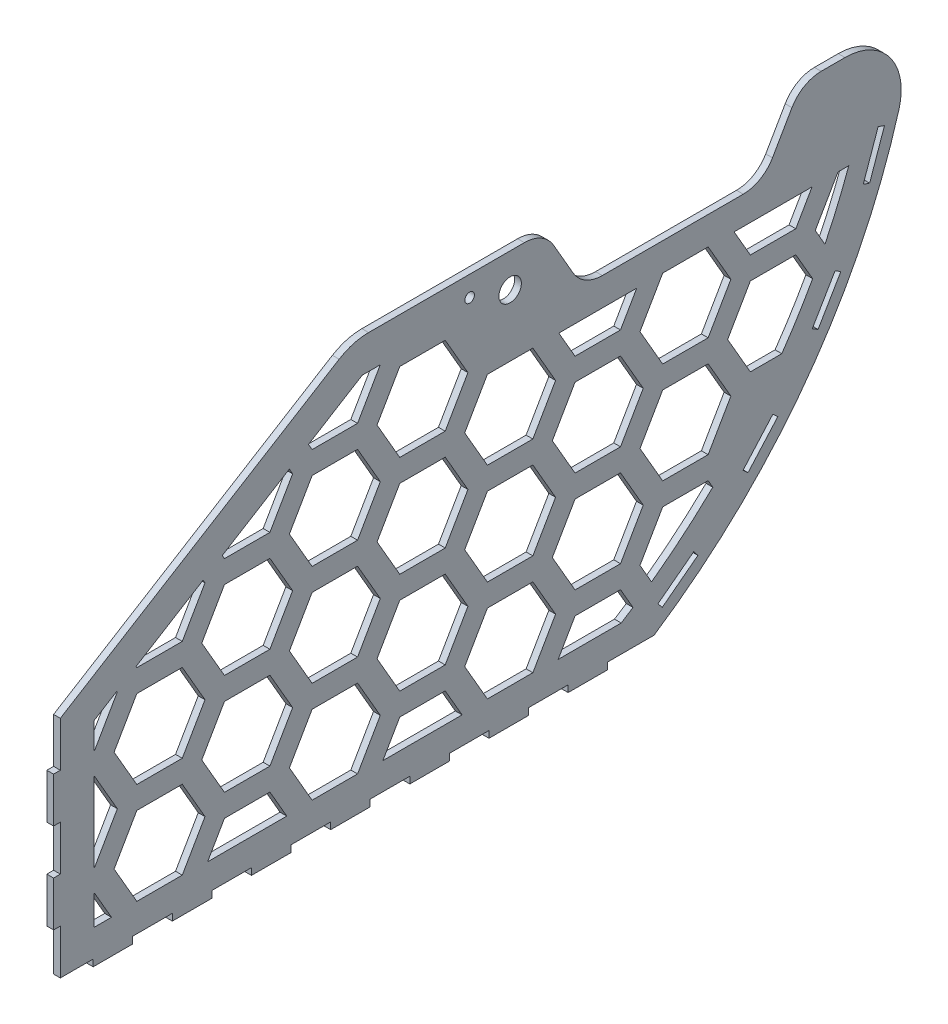
SolidWorks part; units mm, degrees
ref_plane "Front Plane" through (0, 0, 0) normal (0, 0, 1) x (1, 0, 0)
ref_plane "Top Plane" through (0, 0, 0) normal (0, 1, 0) x (1, 0, 0)
ref_plane "Right Plane" through (0, 0, 0) normal (1, 0, 0) x (0, 0, -1)
sketch "Sketch1" plane through (0, 0, 0) normal (1, 0, 0) x (0, 0, -1)
  line L0 (-190, -90) -> (-190, 90)
  line L1 (-190, 90) -> (190, 90)
  line L2 (-190, -90) -> (74, -90)
  line L3 (-193, -93) -> (-175.4, -93) construction
  line L4 (-175.4, -93) -> (-157.8, -93)
  line L5 (-175.4, -93) -> (-175.4, -90)
  line L6 (-175.4, -90) -> (-157.8, -90)
  line L7 (-157.8, -93) -> (-157.8, -90)
  line L8 (-175.4, -93) -> (-157.8, -90) construction
  line L9 (-175.4, -90) -> (-157.8, -93) construction
  line L10 (-140.2, -93) -> (-122.6, -93)
  line L11 (-140.2, -93) -> (-140.2, -90)
  line L12 (-140.2, -90) -> (-122.6, -90)
  line L13 (-122.6, -93) -> (-122.6, -90)
  line L14 (-140.2, -93) -> (-122.6, -90) construction
  line L15 (-140.2, -90) -> (-122.6, -93) construction
  line L16 (-105, -93) -> (-87.4, -93)
  line L17 (-105, -93) -> (-105, -90)
  line L18 (-105, -90) -> (-87.4, -90)
  line L19 (-87.4, -93) -> (-87.4, -90)
  line L20 (-105, -93) -> (-87.4, -90) construction
  line L21 (-105, -90) -> (-87.4, -93) construction
  line L22 (-69.8, -93) -> (-52.2, -93)
  line L23 (-69.8, -93) -> (-69.8, -90)
  line L24 (-69.8, -90) -> (-52.2, -90)
  line L25 (-52.2, -93) -> (-52.2, -90)
  line L26 (-69.8, -93) -> (-52.2, -90) construction
  line L27 (-69.8, -90) -> (-52.2, -93) construction
  line L28 (-34.6, -93) -> (-17, -93)
  line L29 (-34.6, -93) -> (-34.6, -90)
  line L30 (-34.6, -90) -> (-17, -90)
  line L31 (-17, -93) -> (-17, -90)
  line L32 (-34.6, -93) -> (-17, -90) construction
  line L33 (-34.6, -90) -> (-17, -93) construction
  line L34 (0.6, -93) -> (18.2, -93)
  line L35 (0.6, -93) -> (0.6, -90)
  line L36 (0.6, -90) -> (18.2, -90)
  line L37 (18.2, -93) -> (18.2, -90)
  line L38 (0.6, -93) -> (18.2, -90) construction
  line L39 (0.6, -90) -> (18.2, -93) construction
  line L40 (35.8, -93) -> (53.4, -93)
  line L41 (35.8, -93) -> (35.8, -90)
  line L42 (35.8, -90) -> (53.4, -90)
  line L43 (53.4, -93) -> (53.4, -90)
  line L44 (35.8, -93) -> (53.4, -90) construction
  line L45 (35.8, -90) -> (53.4, -93) construction
  line L46 (-157.8, -93) -> (-140.2, -93) construction
  line L47 (-122.6, -93) -> (-105, -93) construction
  line L48 (-87.4, -93) -> (-69.8, -93) construction
  line L49 (-52.2, -93) -> (-34.6, -93) construction
  line L50 (-17, -93) -> (0.6, -93) construction
  line L51 (18.2, -93) -> (35.8, -93) construction
  line L52 (53.4, -93) -> (71, -93) construction
  line L53 (-193, -90) -> (-193, -70) construction
  line L54 (-193, -30) -> (-190, -30)
  line L55 (-193, -30) -> (-193, -10)
  line L56 (-193, -10) -> (-190, -10)
  line L57 (-190, -30) -> (-190, -10)
  line L58 (-193, -30) -> (-190, -10) construction
  line L59 (-193, -10) -> (-190, -30) construction
  line L60 (-193, -70) -> (-190, -70)
  line L61 (-193, -70) -> (-193, -50)
  line L62 (-193, -50) -> (-190, -50)
  line L63 (-190, -70) -> (-190, -50)
  line L64 (-193, -70) -> (-190, -50) construction
  line L65 (-193, -50) -> (-190, -70) construction
  line L66 (-193, -50) -> (-193, -30) construction
  line L67 (-193, -10) -> (-193, 10) construction
  line L68 (-190, 10) -> (-60, 90)
  arc A0 (74, -90) -> (190, 90) centre (-71.9803, 131.454) ccw
  point P5 (-190, 0)
  point P6 (-96.2, -91.5)
  point P8 (0, 90)
  point P9 (-131.4, -91.5)
  point P17 (-166.6, -91.5)
  point P23 (-61, -91.5)
  point P28 (-25.8, -91.5)
  point P33 (9.4, -91.5)
  point P38 (44.6, -91.5)
  point P44 (-191.5, -60)
  point P47 (-191.5, -20)
  dimension "D1" = 180
  dimension "D2" = 380
  dimension "D3" = 264
  dimension "D4" = 3
  dimension "D5" = 100
  dimension "D6" = 3
  dimension "D7" = 130
extrude "Boss-Extrude1" add sketch "Sketch1" along normal mid plane 3 contours L2 A0 L1 L0 | L56 L55 L54 L0 | L62 L61 L60 L0 | L4 L7 L2 L5 | L10 L13 L2 L11 | L16 L19 L2 L17 | L22 L25 L2 L23 | L28 L31 L2 L29 | L40 L43 L2 L41 | L34 L37 L2 L35 region at (0, -0.5729, 6.488) region at (0, -60, 191.5) region at (0, -91.5, 166.6) region at (0, -20, 191.5) region at (0, -91.5, 131.4) region at (0, -91.5, 96.2) region at (0, -91.5, 61) region at (0, -91.5, -44.6) region at (0, -91.5, 25.8) region at (0, -91.5, -9.4)
sketch "Sketch3" plane through (1.5, 0, 0) normal (1, 0, 0) x (0, 0, -1)
  line L0 (144.3362, -7.1911) -> (154.4649, 10.0544)
  line L1 (144.3362, -7.1911) -> (146.923, -8.7104)
  line L2 (154.4649, 10.0544) -> (157.0517, 8.5351)
  line L3 (146.923, -8.7104) -> (157.0517, 8.5351)
  line L4 (144.3362, -7.1911) -> (157.0517, 8.5351) construction
  line L5 (154.4649, 10.0544) -> (146.923, -8.7104) construction
  line L6 (169.8454, 36.1385) -> (176.458, 55.0137)
  line L7 (169.8454, 36.1385) -> (167.0141, 37.1304)
  line L8 (176.458, 55.0137) -> (173.6268, 56.0056)
  line L9 (167.0141, 37.1304) -> (173.6268, 56.0056)
  line L10 (169.8454, 36.1385) -> (173.6268, 56.0056) construction
  line L11 (176.458, 55.0137) -> (167.0141, 37.1304) construction
  line L12 (115.7814, -48.2966) -> (129.046, -33.3282)
  line L13 (115.7814, -48.2966) -> (113.5362, -46.3069)
  line L14 (129.046, -33.3282) -> (126.8007, -31.3385)
  line L15 (113.5362, -46.3069) -> (126.8007, -31.3385)
  line L16 (115.7814, -48.2966) -> (126.8007, -31.3385) construction
  line L17 (129.046, -33.3282) -> (113.5362, -46.3069) construction
  line L18 (75.7706, -78.7482) -> (91.6729, -66.6191)
  line L19 (75.7706, -78.7482) -> (77.5899, -81.1336)
  line L20 (91.6729, -66.6191) -> (93.4922, -69.0044)
  line L21 (77.5899, -81.1336) -> (93.4922, -69.0044)
  line L22 (75.7706, -78.7482) -> (93.4922, -69.0044) construction
  line L23 (91.6729, -66.6191) -> (77.5899, -81.1336) construction
  line L24 (84.6314, -73.8763) -> (121.2911, -39.8175) construction
  line L25 (121.2911, -39.8175) -> (150.694, 0.672) construction
  line L26 (150.694, 0.672) -> (171.7361, 46.072) construction
  line L27 (150.694, 0.672) -> (156.7299, -2.873) construction
  line L28 (121.2911, -39.8175) -> (126.53, -44.4601) construction
  line L29 (84.6314, -73.8763) -> (88.8766, -79.4421) construction
  line L30 (171.7361, 46.072) -> (178.3424, 43.7576) construction
  line L31 (80.9255, -85.5067) -> (96.8278, -73.3775) construction
  line L32 (119.8977, -51.9443) -> (133.1623, -36.9759) construction
  line L33 (151.6655, -11.4958) -> (161.7943, 5.7497) construction
  line L34 (181.6487, 53.1952) -> (175.0361, 34.32) construction
  line L35 (84.6314, -73.8763) -> (65.5, -90) construction
  line L36 (171.7361, 46.072) -> (181.5, 90) construction
  line L37 (53.4, -90) -> (74, -90) construction
  line L38 (-60, 90) -> (190, 90) construction
  line L39 (181.5, 90) -> (190, 90) construction
  line L40 (65.5, -90) -> (74, -90) construction
  line L41 (84.6314, -73.8763) -> (102.9612, -56.8469) construction
  arc A0 (74, -90) -> (190, 90) centre (-71.9803, 131.454) ccw construction
  point P1 (150.694, 0.672)
  point P2 (171.7361, 46.072)
  point P3 (121.2911, -39.8175)
  point P8 (84.6314, -73.8763)
  point P37 (178.3424, 43.7576)
  point P39 (156.7299, -2.873)
  point P43 (126.53, -44.4601)
  point P44 (88.8766, -79.4421)
  dimension "D4" = 8.5
  dimension "D1" = 3
  dimension "D2" = 7
  dimension "D3" = 20
  dimension "D5" = 45
extrude "Cut-Extrude2" cut sketch "Sketch3" against normal through all both and the other way through all
fillet "Fillet1" radius 25 2 edges at (0, 90, -190) (0, 90, 60)
sketch "Sketch4" plane through (1.5, 0, 0) normal (1, 0, 0) x (0, 0, -1)
  circle A0 centre (10, 75) radius 5
  circle A1 centre (-8, 81) radius 2.15
  arc A2 (182.91, 58.0846) -> (158.8854, 90) centre (158.8854, 65) ccw construction
  dimension "D1" = 10
  dimension "D4" = 4.3
  dimension "D6" = 6
  dimension "D2" = 148.8854
  dimension "D3" = 75
  dimension "D5" = 18
extrude "Cut-Extrude3" cut sketch "Sketch4" against normal through all both and the other way through all
sketch "Sketch5" plane through (1.5, 0, 0) normal (1, 0, 0) x (0, 0, -1)
  line L0 (25, 90) -> (42.3205, 60)
  line L1 (-52.9239, 90) -> (158.8854, 90) construction
  line L2 (42.3205, 60) -> (122.3205, 60)
  line L3 (122.3205, 60) -> (139.641, 90)
  circle A0 centre (10, 75) radius 5 construction
  point P8 (136.2989, 70.4297)
  dimension "D1" = 60
  dimension "D2" = 80
  dimension "D3" = 15
  dimension "D4" = 30
extrude "Cut-Extrude5" cut sketch "Sketch5" against normal through all both and the other way through all
sketch "Sketch2" plane through (0, 0, 0) normal (1, 0, 0) x (0, 0, -1)
  line L0 (-96.8098, -20) -> (-117.0171, -20)
  line L1 (-96.8098, -65) -> (-117.0171, -65)
  line L2 (-117.0171, -65) -> (-127.1207, -82.5)
  line L3 (-127.1207, -82.5) -> (-117.0171, -100)
  line L4 (-117.0171, -100) -> (-96.8098, -100)
  line L5 (-96.8098, -100) -> (-86.7062, -82.5)
  line L6 (-86.7062, -82.5) -> (-96.8098, -65)
  line L13 (-117.0171, -20) -> (-127.1207, -37.5)
  line L14 (-88.1495, -105) -> (-78.0459, -122.5)
  line L15 (-78.0459, -122.5) -> (-57.8387, -122.5)
  line L16 (-57.8387, -122.5) -> (-47.735, -105)
  line L17 (-47.735, -105) -> (-57.8387, -87.5)
  line L18 (-57.8387, -87.5) -> (-78.0459, -87.5)
  line L19 (-78.0459, -87.5) -> (-88.1495, -105)
  line L20 (-127.1207, -37.5) -> (-117.0171, -55)
  line L21 (-117.0171, -55) -> (-96.8098, -55)
  line L22 (-96.8098, -55) -> (-86.7062, -37.5)
  line L23 (-86.7062, -37.5) -> (-96.8098, -20)
  line L24 (-88.1495, -60) -> (-78.0459, -77.5)
  line L25 (-78.0459, -77.5) -> (-57.8387, -77.5)
  line L26 (-57.8387, -77.5) -> (-47.735, -60)
  line L27 (-47.735, -60) -> (-57.8387, -42.5)
  line L28 (-57.8387, -42.5) -> (-78.0459, -42.5)
  line L29 (-78.0459, -42.5) -> (-88.1495, -60)
  line L30 (-96.8098, 25) -> (-117.0171, 25)
  line L31 (-117.0171, 25) -> (-127.1207, 7.5)
  line L32 (-127.1207, 7.5) -> (-117.0171, -10)
  line L33 (-117.0171, -10) -> (-96.8098, -10)
  line L34 (-96.8098, -10) -> (-86.7062, 7.5)
  line L35 (-86.7062, 7.5) -> (-96.8098, 25)
  line L36 (-88.1495, -15) -> (-78.0459, -32.5)
  line L37 (-78.0459, -32.5) -> (-57.8387, -32.5)
  line L38 (-57.8387, -32.5) -> (-47.735, -15)
  line L39 (-47.735, -15) -> (-57.8387, 2.5)
  line L40 (-57.8387, 2.5) -> (-78.0459, 2.5)
  line L41 (-78.0459, 2.5) -> (-88.1495, -15)
  line L42 (-96.8098, 70) -> (-117.0171, 70)
  line L43 (-117.0171, 70) -> (-127.1207, 52.5)
  line L44 (-127.1207, 52.5) -> (-117.0171, 35)
  line L45 (-117.0171, 35) -> (-96.8098, 35)
  line L46 (-96.8098, 35) -> (-86.7062, 52.5)
  line L47 (-86.7062, 52.5) -> (-96.8098, 70)
  line L48 (-88.1495, 30) -> (-78.0459, 12.5)
  line L49 (-78.0459, 12.5) -> (-57.8387, 12.5)
  line L50 (-57.8387, 12.5) -> (-47.735, 30)
  line L51 (-47.735, 30) -> (-57.8387, 47.5)
  line L52 (-57.8387, 47.5) -> (-78.0459, 47.5)
  line L53 (-78.0459, 47.5) -> (-88.1495, 30)
  line L54 (-96.8098, 115) -> (-117.0171, 115)
  line L55 (-117.0171, 115) -> (-127.1207, 97.5)
  line L56 (-127.1207, 97.5) -> (-117.0171, 80)
  line L57 (-117.0171, 80) -> (-96.8098, 80)
  line L58 (-96.8098, 80) -> (-86.7062, 97.5)
  line L59 (-86.7062, 97.5) -> (-96.8098, 115)
  line L60 (-88.1495, 75) -> (-78.0459, 57.5)
  line L61 (-78.0459, 57.5) -> (-57.8387, 57.5)
  line L62 (-57.8387, 57.5) -> (-47.735, 75)
  line L63 (-47.735, 75) -> (-57.8387, 92.5)
  line L64 (-57.8387, 92.5) -> (-78.0459, 92.5)
  line L65 (-78.0459, 92.5) -> (-88.1495, 75)
  line L66 (-96.8098, 160) -> (-117.0171, 160)
  line L67 (-117.0171, 160) -> (-127.1207, 142.5)
  line L68 (-127.1207, 142.5) -> (-117.0171, 125)
  line L69 (-117.0171, 125) -> (-96.8098, 125)
  line L70 (-96.8098, 125) -> (-86.7062, 142.5)
  line L71 (-86.7062, 142.5) -> (-96.8098, 160)
  line L72 (-88.1495, 120) -> (-78.0459, 102.5)
  line L73 (-78.0459, 102.5) -> (-57.8387, 102.5)
  line L74 (-57.8387, 102.5) -> (-47.735, 120)
  line L75 (-47.735, 120) -> (-57.8387, 137.5)
  line L76 (-57.8387, 137.5) -> (-78.0459, 137.5)
  line L77 (-78.0459, 137.5) -> (-88.1495, 120)
  line L102 (-96.8098, -65) -> (-96.8098, -20) construction
  line L103 (-78.0459, -87.5) -> (-78.0459, -77.5) construction
  line L104 (-91.758, -73.75) -> (-83.0977, -68.75) construction
  line L105 (-10.2073, 120) -> (-0.1036, 102.5)
  line L106 (-0.1036, 102.5) -> (20.1036, 102.5)
  line L107 (20.1036, 102.5) -> (30.2073, 120)
  line L108 (30.2073, 120) -> (20.1036, 137.5)
  line L109 (20.1036, 137.5) -> (-0.1036, 137.5)
  line L110 (-0.1036, 137.5) -> (-10.2073, 120)
  line L111 (-18.8675, 160) -> (-39.0748, 160)
  line L112 (-39.0748, 160) -> (-49.1784, 142.5)
  line L113 (-49.1784, 142.5) -> (-39.0748, 125)
  line L114 (-39.0748, 125) -> (-18.8675, 125)
  line L115 (-18.8675, 125) -> (-8.7639, 142.5)
  line L116 (-8.7639, 142.5) -> (-18.8675, 160)
  line L117 (-18.8675, 115) -> (-39.0748, 115)
  line L118 (-39.0748, 115) -> (-49.1784, 97.5)
  line L119 (-49.1784, 97.5) -> (-39.0748, 80)
  line L120 (-39.0748, 80) -> (-18.8675, 80)
  line L121 (-18.8675, 80) -> (-8.7639, 97.5)
  line L122 (-8.7639, 97.5) -> (-18.8675, 115)
  line L123 (-18.8675, 70) -> (-39.0748, 70)
  line L124 (-39.0748, 70) -> (-49.1784, 52.5)
  line L125 (-49.1784, 52.5) -> (-39.0748, 35)
  line L126 (-39.0748, 35) -> (-18.8675, 35)
  line L127 (-18.8675, 35) -> (-8.7639, 52.5)
  line L128 (-8.7639, 52.5) -> (-18.8675, 70)
  line L129 (-18.8675, 25) -> (-39.0748, 25)
  line L130 (-39.0748, 25) -> (-49.1784, 7.5)
  line L131 (-49.1784, 7.5) -> (-39.0748, -10)
  line L132 (-39.0748, -10) -> (-18.8675, -10)
  line L133 (-18.8675, -10) -> (-8.7639, 7.5)
  line L134 (-8.7639, 7.5) -> (-18.8675, 25)
  line L135 (-10.2073, -15) -> (-0.1036, -32.5)
  line L136 (-0.1036, -32.5) -> (20.1036, -32.5)
  line L137 (20.1036, -32.5) -> (30.2073, -15)
  line L138 (30.2073, -15) -> (20.1036, 2.5)
  line L139 (20.1036, 2.5) -> (-0.1036, 2.5)
  line L140 (-0.1036, 2.5) -> (-10.2073, -15)
  line L141 (-18.8675, -20) -> (-39.0748, -20)
  line L142 (-39.0748, -20) -> (-49.1784, -37.5)
  line L143 (-49.1784, -37.5) -> (-39.0748, -55)
  line L144 (-39.0748, -55) -> (-18.8675, -55)
  line L145 (-18.8675, -55) -> (-8.7639, -37.5)
  line L146 (-8.7639, -37.5) -> (-18.8675, -20)
  line L147 (-10.2073, -60) -> (-0.1036, -77.5)
  line L148 (-0.1036, -77.5) -> (20.1036, -77.5)
  line L149 (20.1036, -77.5) -> (30.2073, -60)
  line L150 (30.2073, -60) -> (20.1036, -42.5)
  line L151 (20.1036, -42.5) -> (-0.1036, -42.5)
  line L152 (-0.1036, -42.5) -> (-10.2073, -60)
  line L153 (-18.8675, -65) -> (-39.0748, -65)
  line L154 (-39.0748, -65) -> (-49.1784, -82.5)
  line L155 (-49.1784, -82.5) -> (-39.0748, -100)
  line L156 (-39.0748, -100) -> (-18.8675, -100)
  line L157 (-18.8675, -100) -> (-8.7639, -82.5)
  line L158 (-8.7639, -82.5) -> (-18.8675, -65)
  line L159 (-10.2073, -105) -> (-0.1036, -122.5)
  line L160 (-0.1036, -122.5) -> (20.1036, -122.5)
  line L161 (20.1036, -122.5) -> (30.2073, -105)
  line L162 (30.2073, -105) -> (20.1036, -87.5)
  line L163 (20.1036, -87.5) -> (-0.1036, -87.5)
  line L164 (-0.1036, -87.5) -> (-10.2073, -105)
  line L165 (-10.2073, 30) -> (-0.1036, 12.5)
  line L166 (-0.1036, 12.5) -> (20.1036, 12.5)
  line L167 (20.1036, 12.5) -> (30.2073, 30)
  line L168 (30.2073, 30) -> (20.1036, 47.5)
  line L169 (20.1036, 47.5) -> (-0.1036, 47.5)
  line L170 (-0.1036, 47.5) -> (-10.2073, 30)
  line L171 (-10.2073, 75) -> (-0.1036, 57.5)
  line L172 (-0.1036, 57.5) -> (20.1036, 57.5)
  line L173 (20.1036, 57.5) -> (30.2073, 75)
  line L174 (30.2073, 75) -> (20.1036, 92.5)
  line L175 (20.1036, 92.5) -> (-0.1036, 92.5)
  line L176 (-0.1036, 92.5) -> (-10.2073, 75)
  line L177 (67.735, 120) -> (77.8387, 102.5)
  line L178 (77.8387, 102.5) -> (98.0459, 102.5)
  line L179 (98.0459, 102.5) -> (108.1495, 120)
  line L180 (108.1495, 120) -> (98.0459, 137.5)
  line L181 (98.0459, 137.5) -> (77.8387, 137.5)
  line L182 (77.8387, 137.5) -> (67.735, 120)
  line L183 (59.0748, 160) -> (38.8675, 160)
  line L184 (38.8675, 160) -> (28.7639, 142.5)
  line L185 (28.7639, 142.5) -> (38.8675, 125)
  line L186 (38.8675, 125) -> (59.0748, 125)
  line L187 (59.0748, 125) -> (69.1784, 142.5)
  line L188 (69.1784, 142.5) -> (59.0748, 160)
  line L189 (59.0748, 115) -> (38.8675, 115)
  line L190 (38.8675, 115) -> (28.7639, 97.5)
  line L191 (28.7639, 97.5) -> (38.8675, 80)
  line L192 (38.8675, 80) -> (59.0748, 80)
  line L193 (59.0748, 80) -> (69.1784, 97.5)
  line L194 (69.1784, 97.5) -> (59.0748, 115)
  line L195 (59.0748, 70) -> (38.8675, 70)
  line L196 (38.8675, 70) -> (28.7639, 52.5)
  line L197 (28.7639, 52.5) -> (38.8675, 35)
  line L198 (38.8675, 35) -> (59.0748, 35)
  line L199 (59.0748, 35) -> (69.1784, 52.5)
  line L200 (69.1784, 52.5) -> (59.0748, 70)
  line L201 (59.0748, 25) -> (38.8675, 25)
  line L202 (38.8675, 25) -> (28.7639, 7.5)
  line L203 (28.7639, 7.5) -> (38.8675, -10)
  line L204 (38.8675, -10) -> (59.0748, -10)
  line L205 (59.0748, -10) -> (69.1784, 7.5)
  line L206 (69.1784, 7.5) -> (59.0748, 25)
  line L207 (67.735, -15) -> (77.8387, -32.5)
  line L208 (77.8387, -32.5) -> (98.0459, -32.5)
  line L209 (98.0459, -32.5) -> (108.1495, -15)
  line L210 (108.1495, -15) -> (98.0459, 2.5)
  line L211 (98.0459, 2.5) -> (77.8387, 2.5)
  line L212 (77.8387, 2.5) -> (67.735, -15)
  line L213 (59.0748, -20) -> (38.8675, -20)
  line L214 (38.8675, -20) -> (28.7639, -37.5)
  line L215 (28.7639, -37.5) -> (38.8675, -55)
  line L216 (38.8675, -55) -> (59.0748, -55)
  line L217 (59.0748, -55) -> (69.1784, -37.5)
  line L218 (69.1784, -37.5) -> (59.0748, -20)
  line L219 (67.735, -60) -> (77.8387, -77.5)
  line L220 (77.8387, -77.5) -> (98.0459, -77.5)
  line L221 (98.0459, -77.5) -> (108.1495, -60)
  line L222 (108.1495, -60) -> (98.0459, -42.5)
  line L223 (98.0459, -42.5) -> (77.8387, -42.5)
  line L224 (77.8387, -42.5) -> (67.735, -60)
  line L225 (59.0748, -65) -> (38.8675, -65)
  line L226 (38.8675, -65) -> (28.7639, -82.5)
  line L227 (28.7639, -82.5) -> (38.8675, -100)
  line L228 (38.8675, -100) -> (59.0748, -100)
  line L229 (59.0748, -100) -> (69.1784, -82.5)
  line L230 (69.1784, -82.5) -> (59.0748, -65)
  line L231 (67.735, -105) -> (77.8387, -122.5)
  line L232 (77.8387, -122.5) -> (98.0459, -122.5)
  line L233 (98.0459, -122.5) -> (108.1495, -105)
  line L234 (108.1495, -105) -> (98.0459, -87.5)
  line L235 (98.0459, -87.5) -> (77.8387, -87.5)
  line L236 (77.8387, -87.5) -> (67.735, -105)
  line L237 (67.735, 30) -> (77.8387, 12.5)
  line L238 (77.8387, 12.5) -> (98.0459, 12.5)
  line L239 (98.0459, 12.5) -> (108.1495, 30)
  line L240 (108.1495, 30) -> (98.0459, 47.5)
  line L241 (98.0459, 47.5) -> (77.8387, 47.5)
  line L242 (77.8387, 47.5) -> (67.735, 30)
  line L243 (67.735, 75) -> (77.8387, 57.5)
  line L244 (77.8387, 57.5) -> (98.0459, 57.5)
  line L245 (98.0459, 57.5) -> (108.1495, 75)
  line L246 (108.1495, 75) -> (98.0459, 92.5)
  line L247 (98.0459, 92.5) -> (77.8387, 92.5)
  line L248 (77.8387, 92.5) -> (67.735, 75)
  line L249 (145.6773, 120) -> (155.7809, 102.5)
  line L250 (155.7809, 102.5) -> (175.9882, 102.5)
  line L251 (175.9882, 102.5) -> (186.0918, 120)
  line L252 (186.0918, 120) -> (175.9882, 137.5)
  line L253 (175.9882, 137.5) -> (155.7809, 137.5)
  line L254 (155.7809, 137.5) -> (145.6773, 120)
  line L255 (137.0171, 160) -> (116.8098, 160)
  line L256 (116.8098, 160) -> (106.7062, 142.5)
  line L257 (106.7062, 142.5) -> (116.8098, 125)
  line L258 (116.8098, 125) -> (137.0171, 125)
  line L259 (137.0171, 125) -> (147.1207, 142.5)
  line L260 (147.1207, 142.5) -> (137.0171, 160)
  line L261 (137.0171, 115) -> (116.8098, 115)
  line L262 (116.8098, 115) -> (106.7062, 97.5)
  line L263 (106.7062, 97.5) -> (116.8098, 80)
  line L264 (116.8098, 80) -> (137.0171, 80)
  line L265 (137.0171, 80) -> (147.1207, 97.5)
  line L266 (147.1207, 97.5) -> (137.0171, 115)
  line L267 (137.0171, 70) -> (116.8098, 70)
  line L268 (116.8098, 70) -> (106.7062, 52.5)
  line L269 (106.7062, 52.5) -> (116.8098, 35)
  line L270 (116.8098, 35) -> (137.0171, 35)
  line L271 (137.0171, 35) -> (147.1207, 52.5)
  line L272 (147.1207, 52.5) -> (137.0171, 70)
  line L273 (137.0171, 25) -> (116.8098, 25)
  line L274 (116.8098, 25) -> (106.7062, 7.5)
  line L275 (106.7062, 7.5) -> (116.8098, -10)
  line L276 (116.8098, -10) -> (137.0171, -10)
  line L277 (137.0171, -10) -> (147.1207, 7.5)
  line L278 (147.1207, 7.5) -> (137.0171, 25)
  line L279 (145.6773, -15) -> (155.7809, -32.5)
  line L280 (155.7809, -32.5) -> (175.9882, -32.5)
  line L281 (175.9882, -32.5) -> (186.0918, -15)
  line L282 (186.0918, -15) -> (175.9882, 2.5)
  line L283 (175.9882, 2.5) -> (155.7809, 2.5)
  line L284 (155.7809, 2.5) -> (145.6773, -15)
  line L285 (137.0171, -20) -> (116.8098, -20)
  line L286 (116.8098, -20) -> (106.7062, -37.5)
  line L287 (106.7062, -37.5) -> (116.8098, -55)
  line L288 (116.8098, -55) -> (137.0171, -55)
  line L289 (137.0171, -55) -> (147.1207, -37.5)
  line L290 (147.1207, -37.5) -> (137.0171, -20)
  line L291 (145.6773, -60) -> (155.7809, -77.5)
  line L292 (155.7809, -77.5) -> (175.9882, -77.5)
  line L293 (175.9882, -77.5) -> (186.0918, -60)
  line L294 (186.0918, -60) -> (175.9882, -42.5)
  line L295 (175.9882, -42.5) -> (155.7809, -42.5)
  line L296 (155.7809, -42.5) -> (145.6773, -60)
  line L297 (137.0171, -65) -> (116.8098, -65)
  line L298 (116.8098, -65) -> (106.7062, -82.5)
  line L299 (106.7062, -82.5) -> (116.8098, -100)
  line L300 (116.8098, -100) -> (137.0171, -100)
  line L301 (137.0171, -100) -> (147.1207, -82.5)
  line L302 (147.1207, -82.5) -> (137.0171, -65)
  line L303 (145.6773, -105) -> (155.7809, -122.5)
  line L304 (155.7809, -122.5) -> (175.9882, -122.5)
  line L305 (175.9882, -122.5) -> (186.0918, -105)
  line L306 (186.0918, -105) -> (175.9882, -87.5)
  line L307 (175.9882, -87.5) -> (155.7809, -87.5)
  line L308 (155.7809, -87.5) -> (145.6773, -105)
  line L309 (145.6773, 30) -> (155.7809, 12.5)
  line L310 (155.7809, 12.5) -> (175.9882, 12.5)
  line L311 (175.9882, 12.5) -> (186.0918, 30)
  line L312 (186.0918, 30) -> (175.9882, 47.5)
  line L313 (175.9882, 47.5) -> (155.7809, 47.5)
  line L314 (155.7809, 47.5) -> (145.6773, 30)
  line L315 (145.6773, 75) -> (155.7809, 57.5)
  line L316 (155.7809, 57.5) -> (175.9882, 57.5)
  line L317 (175.9882, 57.5) -> (186.0918, 75)
  line L318 (186.0918, 75) -> (175.9882, 92.5)
  line L319 (175.9882, 92.5) -> (155.7809, 92.5)
  line L320 (155.7809, 92.5) -> (145.6773, 75)
  line L321 (-88.1495, 120) -> (-10.2073, 120) construction
  line L322 (-44.1266, -73.75) -> (-52.7868, -68.75) construction
  line L323 (-175, -78) -> (59.3837, -78)
  line L328 (-175, 75) -> (-175, -78)
  line L329 (-0.1036, 92.5) -> (20.1036, 57.5) construction
  line L330 (-175, 75) -> (168.7279, 75)
  line L331 (-69.8, -93) -> (-52.2, -93) construction
  line L332 (-333.9606, 90) -> (-190, 90) construction
  line L333 (-193, -30) -> (-193, -10) construction
  line L334 (-175, 1.6181) -> (-55.7544, 75)
  line L335 (-190, 10) -> (-66.0264, 86.2915) construction
  line L336 (-174.7521, -65) -> (-194.9593, -65)
  line L337 (-194.9593, -65) -> (-205.063, -82.5)
  line L338 (-205.063, -82.5) -> (-194.9593, -100)
  line L339 (-194.9593, -100) -> (-174.7521, -100)
  line L340 (-174.7521, -100) -> (-164.6485, -82.5)
  line L341 (-164.6485, -82.5) -> (-174.7521, -65)
  line L342 (-174.7521, -20) -> (-194.9593, -20)
  line L343 (-194.9593, -20) -> (-205.063, -37.5)
  line L344 (-205.063, -37.5) -> (-194.9593, -55)
  line L345 (-194.9593, -55) -> (-174.7521, -55)
  line L346 (-174.7521, -55) -> (-164.6485, -37.5)
  line L347 (-164.6485, -37.5) -> (-174.7521, -20)
  line L348 (-174.7521, 25) -> (-194.9593, 25)
  line L349 (-194.9593, 25) -> (-205.063, 7.5)
  line L350 (-205.063, 7.5) -> (-194.9593, -10)
  line L351 (-194.9593, -10) -> (-174.7521, -10)
  line L352 (-174.7521, -10) -> (-164.6485, 7.5)
  line L353 (-164.6485, 7.5) -> (-174.7521, 25)
  line L354 (-174.7521, 70) -> (-194.9593, 70)
  line L355 (-194.9593, 70) -> (-205.063, 52.5)
  line L356 (-205.063, 52.5) -> (-194.9593, 35)
  line L357 (-194.9593, 35) -> (-174.7521, 35)
  line L358 (-174.7521, 35) -> (-164.6485, 52.5)
  line L359 (-164.6485, 52.5) -> (-174.7521, 70)
  line L360 (-166.0918, 75) -> (-155.9882, 57.5)
  line L361 (-155.9882, 57.5) -> (-135.7809, 57.5)
  line L362 (-135.7809, 57.5) -> (-125.6773, 75)
  line L363 (-125.6773, 75) -> (-135.7809, 92.5)
  line L364 (-135.7809, 92.5) -> (-155.9882, 92.5)
  line L365 (-155.9882, 92.5) -> (-166.0918, 75)
  line L366 (-166.0918, 30) -> (-155.9882, 12.5)
  line L367 (-155.9882, 12.5) -> (-135.7809, 12.5)
  line L368 (-135.7809, 12.5) -> (-125.6773, 30)
  line L369 (-125.6773, 30) -> (-135.7809, 47.5)
  line L370 (-135.7809, 47.5) -> (-155.9882, 47.5)
  line L371 (-155.9882, 47.5) -> (-166.0918, 30)
  line L372 (-166.0918, -15) -> (-155.9882, -32.5)
  line L373 (-155.9882, -32.5) -> (-135.7809, -32.5)
  line L374 (-135.7809, -32.5) -> (-125.6773, -15)
  line L375 (-125.6773, -15) -> (-135.7809, 2.5)
  line L376 (-135.7809, 2.5) -> (-155.9882, 2.5)
  line L377 (-155.9882, 2.5) -> (-166.0918, -15)
  line L378 (-166.0918, -60) -> (-155.9882, -77.5)
  line L379 (-155.9882, -77.5) -> (-135.7809, -77.5)
  line L380 (-135.7809, -77.5) -> (-125.6773, -60)
  line L381 (-125.6773, -60) -> (-135.7809, -42.5)
  line L382 (-135.7809, -42.5) -> (-155.9882, -42.5)
  line L383 (-155.9882, -42.5) -> (-166.0918, -60)
  line L384 (-166.0918, -105) -> (-155.9882, -122.5)
  line L385 (-155.9882, -122.5) -> (-135.7809, -122.5)
  line L386 (-135.7809, -122.5) -> (-125.6773, -105)
  line L387 (-125.6773, -105) -> (-135.7809, -87.5)
  line L388 (-135.7809, -87.5) -> (-155.9882, -87.5)
  line L389 (-155.9882, -87.5) -> (-166.0918, -105)
  line L390 (-122.0689, -73.75) -> (-130.7291, -68.75) construction
  line L391 (15.7735, 75) -> (31.6506, 47.5)
  line L392 (31.6506, 47.5) -> (144.2339, 47.5)
  line L393 (42.3205, 60) -> (25, 90) construction
  circle A0 centre (-106.9134, -82.5) radius 17.5 construction
  circle A1 centre (-67.9423, -105) radius 17.5 construction
  arc A2 (74, -90) -> (182.91, 58.0846) centre (-71.9803, 131.454) ccw construction
  circle A3 centre (10, 75) radius 5 construction
  arc A6 (59.3837, -78) -> (168.7279, 75) centre (-71.9803, 131.454) ccw
  point P10 (-78.0459, -82.5)
  point P315 (10, 75)
  point P383 (149.8344, 47.5)
  dimension "D3" = 35
  dimension "D5" = 18
  dimension "D2" = 45
  dimension "D6" = 18
  dimension "D7" = 15
  dimension "D8" = 15
  dimension "D9" = 15
  dimension "D1" = 6
  dimension "D4" = 4
  dimension "D10" = 2
extrude "Cut-Extrude1" cut sketch "Sketch2" against normal through all both and the other way through all contours L2 L323 L6 L1 | L28 L29 L24 L25 L26 L27 | L154 L323 L158 L153 | L151 L152 L147 L148 L149 L150 | L323 A6 L230 L225 L226 | L219 A6 L222 L223 L224 | L211 L212 L207 L208 L209 L210 | L217 L218 L213 L214 L215 L216 | L139 L140 L135 L136 L137 L138 | L145 L146 L141 L142 L143 L144 | L40 L41 L36 L37 L38 L39 | L22 L23 L0 L13 L20 L21 | L382 L383 L378 L379 L380 L381 | L346 L347 L342 L328 L345 | L323 L341 L336 L328 | L352 L353 L334 L328 L351 | L376 L377 L372 L373 L374 L375 | L368 L369 L334 L366 L367 | L34 L35 L30 L31 L32 L33 | L334 L44 L45 L46 L47 | L52 L53 L48 L49 L50 L51 | L334 L60 L61 L62 L330 | L127 L128 L123 L124 L125 L126 | L133 L134 L129 L130 L131 L132 | L169 L170 L165 L166 L167 L168 | L392 L391 L195 L196 L197 L198 L199 | L205 L206 L201 L202 L203 L204 | L241 L242 L237 L238 L239 L240 | L276 A6 L278 L273 L274 L275 | L392 L269 L270 L271 | L309 A6 L313 L314 region at (0, -37.5, 106.9134) region at (0, -72.0868, 106.9134) region at (0, 41.7982, -126.9134) region at (0, 30, -87.9423) region at (0, -72.0868, 28.9711) region at (0, -73.5324, 172.413) region at (0, -71.9205, -48.4654) region at (0, -37.5, 171.5476) region at (0, -52.8948, -82.2055) region at (0, -0.1961, 171.4175) region at (0, 19.2216, 139.1315) region at (0, 8.3979, -125.4558) region at (0, 42.3282, 100.5998) region at (0, 35.8836, -152.8052) region at (0, 64.8781, 62.5783) region at (0, 41.7982, -48.9711) region at (0, -60, 67.9423) region at (0, 7.5, 106.9134) region at (0, -15, 67.9423) region at (0, 30, 67.9423) region at (0, 52.5, 28.9711) region at (0, 7.5, 28.9711) region at (0, -15, -10) region at (0, -37.5, 28.9711) region at (0, -60, -10) region at (0, 30, -10) region at (0, 7.5, -48.9711) region at (0, -15, -87.9423) region at (0, -37.5, -48.9711) region at (0, -15, 145.8846) region at (0, -60, 145.8846)
fillet "Fillet2" radius 15 4 edges at (0, 60, -122.3205) (0, 60, -42.3205) (0, 90, -25) (0, 90, -139.641)
equation "\"bottomLength\"= 270mm"
equation "\"topLength\"= 380mm"
equation "\"frontHeight\"= 100mm"
equation "\"height\"= 180mm"
equation "\"width\"= 180mm"
equation "\"D2@Sketch1\"=\"topLength\""
equation "\"D3@Sketch1\"=\"bottomLength\"-6"
equation "\"D1@Sketch1\"=\"height\""
equation "\"D5@Sketch1\"=\"frontHeight\""
